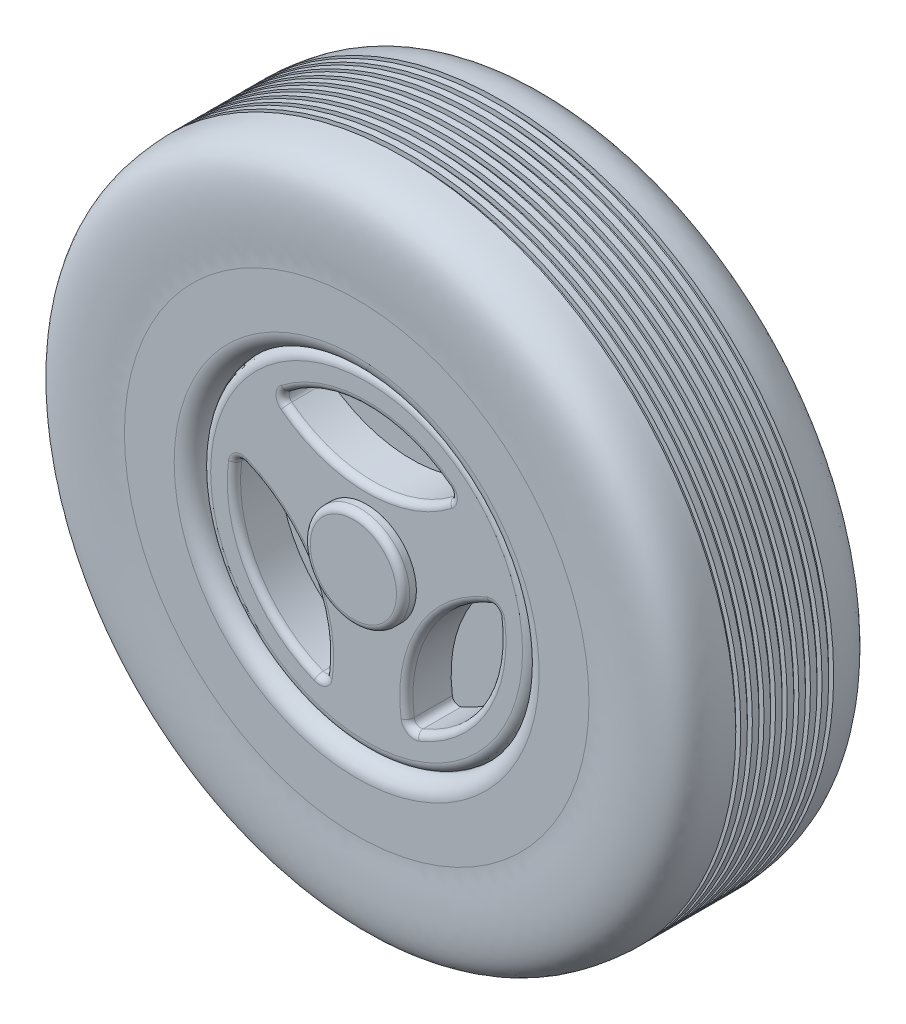
SolidWorks part; units mm, degrees
ref_plane "Top Plane" through (0, 0, 0) normal (0, 0, 1) x (1, 0, 0)
ref_plane "Front Plane" through (0, 0, 0) normal (0, 1, 0) x (1, 0, 0)
ref_plane "Right Plane" through (0, 0, 0) normal (1, 0, 0) x (0, 0, -1)
sketch "Sketch1" plane through (0, 0, 0) normal (-1, 0, 0) x (0, 0, 1)
  line L0 (0, 0) -> (0, -80.7143) construction
  line L1 (-21, -50) -> (-26, -50)
  line L2 (-21, -45) -> (21, -45)
  line L3 (-21, -45) -> (-21, -50)
  line L4 (-26, -50) -> (-26, -40)
  line L5 (21, -45) -> (21, -50)
  line L6 (-26, -40) -> (26, -40)
  line L7 (26, -40) -> (26, -50)
  line L8 (26, -50) -> (21, -50)
  line L9 (-101.7915, 0) -> (99.9025, 0) construction
  dimension "D1" = 45
  dimension "D2" = 5
  dimension "D3" = 21
  dimension "D4" = 42
  dimension "D5" = 5
  dimension "D6" = 5
  dimension "D7" = 5
revolve "Revolve1" add sketch "Sketch1" angle 360 about L9
sketch "Sketch3" plane through (0, 0, 26) normal (0, 0, 1) x (1, 0, 0)
  line L0 (0, 60) -> (-51.9615, -30) construction
  line L1 (-51.9615, -30) -> (51.9615, -30) construction
  line L2 (51.9615, -30) -> (0, 60) construction
  circle A0 centre (0, 0) radius 20 construction
  arc A1 (-26.4575, 30) -> (26.4575, 30) centre (0, 60) ccw
  arc A2 (-12.752, -37.9129) -> (-39.2095, 7.9129) centre (-51.9615, -30) ccw
  arc A3 (39.2095, 7.9129) -> (12.752, -37.9129) centre (51.9615, -30) ccw
  circle A4 centre (0, 0) radius 40 construction
  arc A5 (-12.752, -37.9129) -> (12.752, -37.9129) centre (0, 0) ccw
  arc A6 (-26.4575, 30) -> (-39.2095, 7.9129) centre (0, 0) ccw
  arc A7 (39.2095, 7.9129) -> (26.4575, 30) centre (0, 0) ccw
  dimension "D1" = 40
  dimension "D2" = 80
extrude "Boss-Extrude1" add sketch "Sketch3" against normal up to surface (52 mm away) up to face at (-50, 0, -26)
sketch "Sketch4" plane through (0, 0, 26) normal (0, 0, 1) x (1, 0, 0)
  circle A0 centre (0, 0) radius 15
  dimension "D1" = 30
extrude "Boss-Extrude2" add sketch "Sketch4" along normal blind 4 separate body
fillet "Fillet4" radius 2 1 edges at (15, 0, 30)
mirror "Mirror3" about plane through (0, 0, 0) normal (0, 0, 1) of "Boss-Extrude2", "Fillet4"
fillet "Fillet1" radius 2 4 edges at (-50, 0, -21) (-50, 0, 21) (-45, 0, -21) (-45, 0, 21)
fillet "Fillet2" radius 3 2 edges at (-50, 0, -26) (-50, 0, 26)
fillet "Fillet3" radius 2 18 edges at (0, 40, 26) (0, 40, -26) (-34.641, -20, 26) (-34.641, -20, -26) (17.3205, -10, -26) (17.3205, -10, 26) (0, 20, -26) (0, 20, 26) (26.4575, 30, 0) (-26.4575, 30, 0) (-17.3205, -10, -26) (-17.3205, -10, 26) (-39.2095, 7.9129, 0) (-12.752, -37.9129, 0) (34.641, -20, -26) (12.752, -37.9129, 0) (39.2095, 7.9129, 0) (34.641, -20, 26)
sketch "Sketch8" plane through (0, 0, 0) normal (0, 0, 1) x (1, 0, 0)
  arc A0 (-36.889, 7.0516) -> (-39.6239, 5.4726) centre (-37.6427, 5.199) ccw construction
  arc A1 (-39.6239, 5.4726) -> (-15.0725, -37.0516) centre (0, 0) ccw construction
  arc A2 (-15.0725, -37.0516) -> (-12.3377, -35.4726) centre (-14.3189, -35.199) ccw construction
  arc A3 (-12.3377, -35.4726) -> (-36.889, 7.0516) centre (-51.9615, -30) ccw construction
  arc A4 (12.3377, -35.4726) -> (15.0725, -37.0516) centre (14.3189, -35.199) ccw construction
  arc A5 (36.889, 7.0516) -> (12.3377, -35.4726) centre (51.9615, -30) ccw construction
  arc A6 (39.6239, 5.4726) -> (36.889, 7.0516) centre (37.6427, 5.199) ccw construction
  arc A7 (15.0725, -37.0516) -> (39.6239, 5.4726) centre (0, 0) ccw construction
  arc A8 (-24.5514, 31.5789) -> (-24.5514, 28.4211) centre (-23.3238, 30) ccw construction
  arc A9 (-24.5514, 28.4211) -> (24.5514, 28.4211) centre (0, 60) ccw construction
  arc A10 (24.5514, 31.5789) -> (-24.5514, 31.5789) centre (0, 0) ccw construction
  arc A11 (24.5514, 28.4211) -> (24.5514, 31.5789) centre (23.3238, 30) ccw construction
  arc A12 (-36.889, 7.0516) -> (-39.6239, 5.4726) centre (-37.6427, 5.199) ccw
  arc A13 (-39.6239, 5.4726) -> (-15.0725, -37.0516) centre (0, 0) ccw
  arc A14 (-15.0725, -37.0516) -> (-12.3377, -35.4726) centre (-14.3189, -35.199) ccw
  arc A15 (-12.3377, -35.4726) -> (-36.889, 7.0516) centre (-51.9615, -30) ccw
  arc A16 (12.3377, -35.4726) -> (15.0725, -37.0516) centre (14.3189, -35.199) ccw
  arc A17 (36.889, 7.0516) -> (12.3377, -35.4726) centre (51.9615, -30) ccw
  arc A18 (39.6239, 5.4726) -> (36.889, 7.0516) centre (37.6427, 5.199) ccw
  arc A19 (15.0725, -37.0516) -> (39.6239, 5.4726) centre (0, 0) ccw
  arc A20 (-24.5514, 31.5789) -> (-24.5514, 28.4211) centre (-23.3238, 30) ccw
  arc A21 (-24.5514, 28.4211) -> (24.5514, 28.4211) centre (0, 60) ccw
  arc A22 (24.5514, 31.5789) -> (-24.5514, 31.5789) centre (0, 0) ccw
  arc A23 (24.5514, 28.4211) -> (24.5514, 31.5789) centre (23.3238, 30) ccw
extrude "Boss-Extrude4" add sketch "Sketch8" along normal blind 12.5 and the other way blind 12.5
sketch "Sketch6" plane through (0, 0, 0) normal (1, 0, 0) x (0, 0, -1)
  line L0 (-29, 50) -> (-21, 50)
  line L1 (-21, 50) -> (-21, 47)
  line L2 (-21, 47) -> (0, 47)
  line L3 (0, 47) -> (0, 98.5)
  line L4 (-0.75, 100) -> (-2.75, 100)
  line L5 (-29, 70) -> (-29, 50)
  line L6 (-11.25, 100) -> (-13.25, 100)
  line L7 (-26, 47) -> (-26, -47) construction
  line L8 (-7.75, 100) -> (-9.75, 100)
  line L9 (-4.25, 100) -> (-6.25, 100)
  line L10 (-102.5526, 0) -> (104.4747, 0) construction
  line L13 (0, 98.5) -> (-0.75, 98.5)
  line L14 (-0.75, 100) -> (-0.75, 98.5)
  line L16 (-2.75, 100) -> (-2.75, 98.5)
  line L17 (-2.75, 98.5) -> (-4.25, 98.5)
  line L18 (-4.25, 100) -> (-4.25, 98.5)
  line L20 (-6.25, 100) -> (-6.25, 98.5)
  line L21 (-6.25, 98.5) -> (-7.75, 98.5)
  line L22 (-7.75, 100) -> (-7.75, 98.5)
  line L24 (-9.75, 100) -> (-9.75, 98.5)
  line L25 (-9.75, 98.5) -> (-11.25, 98.5)
  line L26 (-11.25, 100) -> (-11.25, 98.5)
  line L28 (-13.25, 100) -> (-13.25, 98.5)
  line L29 (-13.25, 98.5) -> (-14.75, 98.5)
  line L30 (-14.75, 100) -> (-14.75, 98.5)
  spline S0 degree 3 poles (-29, 70) (-29, 74.6412) (-33.0892, 99.6628) (-17.8268, 99.6742) (-14.75, 100) knots 0 0 0 0 0.508798 0.895542 0.895542 0.895542 0.895542
  dimension "D5" = 5
  dimension "D2" = 20
  dimension "D3" = 3
  dimension "D1" = 100
  dimension "D4" = 1.6
  dimension "D7" = 0.75
  dimension "D8" = 1.5
  dimension "D9" = 1.5
  dimension "D11" = 1.5
  dimension "D12" = 2
  dimension "D13" = 2
  dimension "D10" = 1.5
  dimension "D14" = 1.5
  dimension "D15" = 2
  dimension "D16" = 2
  dimension "D6" = 0
revolve "Revolve2" add sketch "Sketch6" angle 360 about L10
fillet "Fillet6" radius 5 1 edges at (50, 0, 29)
mirror "Mirror4" of "Fillet6", "Revolve2"
equation "\"D4@Sketch1\"=\"D3@Sketch1\"*2"
equation "\"D6@Sketch1\"=\"D5@Sketch1\""
equation "\"D7@Sketch1\"=\"D5@Sketch1\""
equation "\"D8@Sketch6\"=\"D7@Sketch6\"*2"
equation "\"D9@Sketch6\"=\"D8@Sketch6\""
equation "\"D13@Sketch6\"=\"D12@Sketch6\""
equation "\"D10@Sketch6\"=\"D8@Sketch6\""
equation "\"D14@Sketch6\"=\"D8@Sketch6\""
